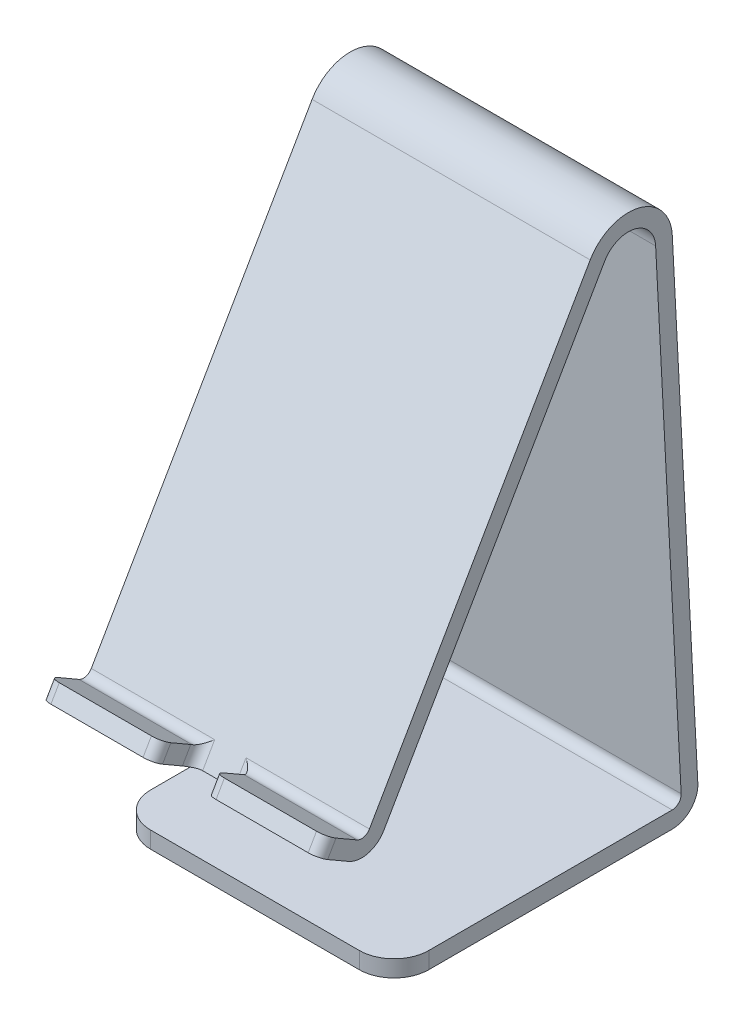
SolidWorks part; units mm, degrees
material "6061-T6 (SS)"
ref_plane "Front Plane" through (0, 0, 0) normal (0, 0, 1) x (1, 0, 0)
ref_plane "Top Plane" through (0, 0, 0) normal (0, 1, 0) x (1, 0, 0)
ref_plane "Right Plane" through (0, 0, 0) normal (1, 0, 0) x (0, 0, -1)
sketch "Sketch1" plane through (0, 0, 0) normal (1, 0, 0) x (0, 0, -1)
  line L0 (-45, 40) -> (18.5085, 150)
  line L1 (-40, 0) -> (40, 0)
  line L2 (-51.8301, 38.1699) -> (-47.5, 35.6699) construction
  line L3 (-47.5, 35.6699) -> (-45, 40) construction
  line L4 (44.9931, 5.2617) -> (37.6486, 145.4049)
  line L5 (44.9931, 5.2617) -> (44.9931, 137.2531) construction
  line L6 (-51.8301, 38.1699) -> (-60.4904, 43.1699)
  arc A0 (-45, 40) -> (-51.8301, 38.1699) centre (-49.3301, 42.5) cw
  arc A1 (18.5085, 150) -> (37.6486, 145.4049) centre (27.398, 144.8677) cw
  arc A2 (40, 0) -> (44.9931, 5.2617) centre (40, 5) ccw
  point P4 (0, 0)
  point P6 (0, 0)
  point P7 (0, 0)
  dimension "D2" = 40
  dimension "D7" = 150
  dimension "D6" = 5
  dimension "D1" = 80
  dimension "D3" = 5
  dimension "D4" = 60
  dimension "D5" = 5
  dimension "D8" = 3
  dimension "D9" = 10
surface "Surface-Extrude1" sketch "Sketch1" parameters "D1"=80
sketch "Sketch2" plane through (0, 0, 0) normal (0, 1, 0) x (1, 0, 0)
  line L0 (40, -40) -> (35.107, 40)
  line L2 (35.107, 40) -> (40, 40)
  line L3 (40, 40) -> (40, -40)
  line L4 (40, 40) -> (-40, 40) construction
  line L5 (0, 40) -> (0, -100) construction
  line L6 (-35.107, 40) -> (-40, 40)
  line L7 (-40, -40) -> (-35.107, 40)
  line L8 (-40, 40) -> (-40, -40)
  dimension "D1" = 3.5
surface "Surface-Trim1" [suppressed]
sketch3d "3DSketch1" [suppressed]
  line L0 (40, 5.2617, -44.9931) -> (-40, 5.2617, -44.9931) construction
  line L1 (40, 0, 40) -> (35.107, 0, -40) construction
  line L2 (-35.107, 0, -40) -> (-40, 0, -40)
  line L3 (-34.5773, 5.2617, -44.9931) -> (-40, 5.2617, -44.9931)
  line L4 (-35.107, 0, -40) -> (-40, 0, 40) construction
  line L7 (34.5773, 5.2617, -44.9931) -> (40, 5.2617, -44.9931)
  line L8 (35.107, 0, -40) -> (40, 0, -40)
  arc A1 (40, 0, -40) -> (40, 5.2617, -44.9931) centre (40, 5, -40) ccw construction
  arc A5 (40, 0, -40) -> (40, 5.2617, -44.9931) centre (40, 5, -40) ccw
  arc A6 (34.5773, 5.2617, -44.9931) -> (35.107, 0, -40) centre (34.8939, 5.0176, -39.987) cw
  arc A7 (-35.107, 0, -40) -> (-34.5773, 5.2617, -44.9931) centre (-34.8939, 5.0176, -39.987) ccw
  arc A8 (-40, 5.2617, -44.9931) -> (-40, 0, -40) centre (-40, 5, -40) cw
  point P1 (34.8189, 1.557, -43.6257)
  point P2 (45, 5, -40)
  point P10 (29.8857, 4.8041, -39.6807)
  point P17 (-29.8857, 4.8041, -39.6807)
  point P21 (45, 5, -40)
  point P23 (-45, 5, -40)
surface "Surface-Trim2" [suppressed]
sketch "Sketch5" plane through (0, 29.4856, 51.0705) normal (0, -0.5, -0.866) x (1, 0, 0)
  line L13 (-40, -12.141) -> (-40, -139.1581)
  line L14 (-40, -139.1581) -> (-35.5645, -139.1581)
  line L15 (40, -139.1581) -> (-40, -139.1581) construction
  line L16 (-35.5645, -139.1581) -> (-40, -12.141)
  line L17 (0, -60.0066) -> (0, 60.0066) construction
  line L18 (40, -139.1581) -> (35.5645, -139.1581)
  line L19 (40, -12.141) -> (40, -139.1581)
  line L20 (35.5645, -139.1581) -> (40, -12.141)
  dimension "D1" = 2
surface "Surface-Trim4" [suppressed]
sketch3d "3DSketch2" [suppressed]
  line L0 (40, 145.4049, -37.6486) -> (-40, 145.4049, -37.6486) construction
  line L2 (35.5645, 145.4049, -37.6486) -> (40, 145.4049, -37.6486)
  line L3 (35.5645, 150, -18.5085) -> (40, 150, -18.5085)
  line L4 (-35.5645, 150, -18.5085) -> (-40, 150, -18.5085)
  line L5 (-35.5645, 145.4049, -37.6486) -> (-40, 145.4049, -37.6486)
  arc A0 (35.5645, 150, -18.5085) -> (35.5645, 145.4049, -37.6486) centre (35.5645, 144.8677, -27.398) cw
  arc A1 (40, 145.4049, -37.6486) -> (40, 150, -18.5085) centre (40, 144.8677, -27.398) ccw construction
  arc A2 (40, 145.4049, -37.6486) -> (40, 150, -18.5085) centre (40, 144.8677, -27.398) ccw
  arc A3 (-40, 150, -18.5085) -> (-40, 145.4049, -37.6486) centre (-40, 144.8677, -27.398) cw
  arc A4 (-35.5645, 145.4049, -37.6486) -> (-35.5645, 150, -18.5085) centre (-35.5645, 144.8677, -27.398) ccw
  point P2 (25.2998, 144.8677, -27.398)
  point P8 (35.5645, 134.8866, -25.0017)
  point P15 (50.2646, 144.8677, -27.398)
  point P16 (50.2646, 144.8677, -27.398)
  point P19 (-50.2646, 144.8677, -27.398)
  point P23 (-25.2998, 144.8677, -27.398)
surface "Surface-Trim5" [suppressed]
sketch "Sketch4" [suppressed] plane through (0, 2.3659, -45.1449) normal (0, -0.0523, 0.9986) x (1, 0, 0)
  line L8 (40, 2.8997) -> (40, 143.2352) construction
  line L15 (40, 143.2352) -> (40, 2.8997)
  line L18 (34.5773, 2.8997) -> (40, 2.8997) construction
  line L19 (40, 2.8997) -> (34.5773, 2.8997)
  line L21 (35.5645, 143.2352) -> (34.5773, 2.8997)
  line L22 (35.5645, 143.2352) -> (40, 143.2352)
  line L28 (34.5773, 2.8997) -> (-34.5773, 2.8997) construction
  line L29 (0, -55) -> (0, 55) construction
  line L30 (-35.5645, 143.2352) -> (-40, 143.2352)
  line L31 (-35.5645, 143.2352) -> (-34.5773, 2.8997)
  line L32 (-40, 2.8997) -> (-34.5773, 2.8997)
  line L33 (-40, 143.2352) -> (-40, 2.8997)
surface "Surface-Trim6" [suppressed]
sketch3d "3DSketch3" [suppressed]
  line L0 (-45, 20, 65) -> (-20, 60, 130)
  line L1 (45, 20, 65) -> (-45, 20, 65) construction
  line L2 (-45, 20, 76.3137) -> (-20, 64.7814, 140.2537)
  line L3 (45, 20, 76.3137) -> (-45, 20, 76.3137) construction
  line L4 (-20, 60, 130) -> (-20, 64.7814, 140.2537) construction
  line L11 (20, 60, 130) -> (20, 64.7814, 140.2537) construction
  line L12 (45, 20, 76.3137) -> (20, 64.7814, 140.2537)
  line L13 (45, 20, 65) -> (20, 60, 130)
  line L14 (-20, 59.8831, 135.1269) -> (-20, 62.3907, 135.1269) construction
  arc A0 (-45, 20, 65) -> (-45, 20, 76.3137) centre (-45, 25.6569, 70.6569) cw
  arc A1 (20, 60, 130) -> (20, 64.7814, 140.2537) centre (20, 67.5175, 132.7362) ccw
  arc A2 (-45, 20, 65) -> (-45, 20, 76.3137) centre (-45, 25.6569, 70.6569) ccw construction
  arc A3 (-20, 64.7814, 140.2537) -> (-20, 60, 130) centre (-20, 67.5175, 132.7362) cw
  arc A4 (45, 20, 76.3137) -> (45, 20, 65) centre (45, 25.6569, 70.6569) ccw
  point P11 (-53, 25.6569, 70.6569)
  point P15 (-53, 25.6569, 70.6569)
  point P17 (-12, 67.5175, 132.7362)
  point P18 (-20, 60.2671, 136.1171)
  point P30 (12, 67.5175, 132.7362)
  point P34 (53, 25.6569, 70.6569)
  dimension "D1" = 40
thicken "Thicken1" surfaces to thicken 101 thickness 2.4 thickness side both sides parameters "D1"=2.4
sketch "Sketch7" plane through (0, 30.6856, 53.149) normal (0, 0.5, 0.866) x (1, 0, 0)
  line L0 (-30.736, 134.1581) -> (0, 1014.3226) construction
  line L1 (30.736, 134.1581) -> (0, 1014.3226) construction
  line L2 (-13.7263, 133.5739) -> (-7.783, 120.5739)
  line L3 (-23.2255, 120.6692) -> (-15.4953, 133.6692)
  line L5 (-8.6925, 119.1581) -> (-22.366, 119.1581)
  line L6 (-6.8527, 132.7423) -> (-0.9095, 119.7423)
  line L7 (0.9095, 119.7423) -> (6.8527, 132.7423)
  line L8 (5.9433, 134.1581) -> (-5.9433, 134.1581)
  line L11 (31.2237, 120.193) -> (30.7697, 133.193)
  line L12 (29.3648, 119.647) -> (21.6346, 132.647)
  line L13 (-30.7697, 133.193) -> (-31.2237, 120.193)
  line L14 (-29.3648, 119.647) -> (-21.6346, 132.647)
  line L15 (-22.4941, 134.1581) -> (-29.7703, 134.1581)
  line L17 (-34.8223, 17.141) -> (34.8223, 17.141)
  line L18 (34.8223, 17.141) -> (30.736, 134.1581)
  line L19 (30.736, 134.1581) -> (-30.736, 134.1581)
  line L20 (-30.736, 134.1581) -> (-34.8223, 17.141)
  line L21 (-34.8223, 17.141) -> (34.8223, 17.141) construction
  line L22 (34.8223, 17.141) -> (30.736, 134.1581) construction
  line L23 (30.736, 134.1581) -> (-30.736, 134.1581) construction
  line L24 (-30.736, 134.1581) -> (-34.8223, 17.141) construction
  line L27 (22.4941, 134.1581) -> (29.7703, 134.1581)
  line L28 (13.7263, 133.5739) -> (7.783, 120.5739)
  line L29 (8.6925, 119.1581) -> (22.366, 119.1581)
  line L30 (23.2255, 120.6692) -> (15.4953, 133.6692)
  line L31 (0, 17.141) -> (0, 1014.3226) construction
  line L32 (-31.2598, 119.1581) -> (-24.1241, 119.1581)
  line L33 (-7.1358, 119.1581) -> (0, 119.1581)
  line L34 (7.1358, 119.1581) -> (0, 119.1581)
  line L35 (24.1241, 119.1581) -> (31.2598, 119.1581)
  line L36 (-31.3646, 116.1581) -> (31.3646, 116.1581) construction
  line L43 (0.9023, 112.5892) -> (7.1135, 99.5892)
  line L44 (-7.1135, 99.5892) -> (-0.9023, 112.5892)
  line L45 (6.2112, 98.1581) -> (-6.2112, 98.1581)
  line L46 (-22.7888, 111.6746) -> (-15.6085, 98.6746)
  line L47 (-8.522, 113.1581) -> (-21.9134, 113.1581)
  line L48 (-13.8309, 98.727) -> (-7.6197, 111.727)
  line L49 (-29.6283, 112.6416) -> (-22.4481, 99.6416)
  line L50 (-31.957, 99.193) -> (-31.5031, 112.193)
  line L51 (-23.3234, 98.1581) -> (-30.9576, 98.1581)
  line L52 (-31.9932, 98.1581) -> (31.9932, 98.1581) construction
  line L53 (-31.4694, 113.1581) -> (31.4694, 113.1581) construction
  line L54 (0, 1014.3226) -> (-24.3237, 17.141) construction
  line L55 (0, 1014.3226) -> (-7.8575, 17.141) construction
  line L56 (-29.9136, 113.1581) -> (-23.6081, 113.1581)
  line L57 (-6.9359, 113.1581) -> (-0.6305, 113.1581)
  line L58 (8.522, 113.1581) -> (21.9134, 113.1581)
  line L59 (13.8309, 98.727) -> (7.6197, 111.727)
  line L60 (22.7888, 111.6746) -> (15.6085, 98.6746)
  line L61 (31.957, 99.193) -> (31.5031, 112.193)
  line L62 (23.3234, 98.1581) -> (30.9576, 98.1581)
  line L63 (29.6283, 112.6416) -> (22.4481, 99.6416)
  line L64 (-32.0979, 95.1581) -> (32.0979, 95.1581) construction
  line L65 (-7.1748, 90.7234) -> (-0.9006, 77.7234)
  line L66 (6.2742, 92.1581) -> (-6.2742, 92.1581)
  line L67 (0.9006, 77.7234) -> (7.1748, 90.7234)
  line L68 (-8.5514, 77.1581) -> (-22.998, 77.1581)
  line L69 (-13.925, 91.5927) -> (-7.6508, 78.5927)
  line L70 (-23.8446, 78.6903) -> (-15.6722, 91.6903)
  line L71 (-32.2364, 91.193) -> (-32.6904, 78.193)
  line L72 (-23.5186, 92.1581) -> (-31.237, 92.1581)
  line L73 (-30.8444, 77.6259) -> (-22.672, 90.6259)
  line L74 (-32.2027, 92.1581) -> (32.2027, 92.1581) construction
  line L75 (-32.7265, 77.1581) -> (32.7265, 77.1581) construction
  line L76 (-21.7087, 92.1581) -> (-15.3781, 92.1581)
  line L77 (-14.1978, 92.1581) -> (-7.8672, 92.1581)
  line L78 (32.2364, 91.193) -> (32.6904, 78.193)
  line L79 (23.5186, 92.1581) -> (31.237, 92.1581)
  line L80 (30.8444, 77.6259) -> (22.672, 90.6259)
  line L81 (23.8446, 78.6903) -> (15.6722, 91.6903)
  line L82 (13.925, 91.5927) -> (7.6508, 78.5927)
  line L83 (8.5514, 77.1581) -> (22.998, 77.1581)
  line L84 (-32.8313, 74.1581) -> (32.8313, 74.1581) construction
  line L85 (-7.4354, 57.6076) -> (-0.8933, 70.6076)
  line L86 (6.5421, 56.1581) -> (-6.5421, 56.1581)
  line L87 (0.8933, 70.6076) -> (7.4354, 57.6076)
  line L88 (-23.8904, 69.6523) -> (-16.2679, 56.6523)
  line L89 (-14.512, 56.7085) -> (-7.9699, 69.7085)
  line L90 (-8.8632, 71.1581) -> (-23.0277, 71.1581)
  line L91 (-33.4237, 57.193) -> (-32.9697, 70.193)
  line L92 (-24.3479, 56.1581) -> (-32.4243, 56.1581)
  line L93 (-31.1077, 70.6639) -> (-23.4853, 57.6639)
  line L94 (-32.936, 71.1581) -> (32.936, 71.1581) construction
  line L95 (-33.4598, 56.1581) -> (33.4598, 56.1581) construction
  line L96 (-31.3975, 71.1581) -> (-24.7733, 71.1581)
  line L97 (-7.2404, 71.1581) -> (-0.6162, 71.1581)
  line L98 (24.3479, 56.1581) -> (32.4243, 56.1581)
  line L99 (31.1077, 70.6639) -> (23.4853, 57.6639)
  line L100 (33.4237, 57.193) -> (32.9697, 70.193)
  line L101 (8.8632, 71.1581) -> (23.0277, 71.1581)
  line L102 (14.512, 56.7085) -> (7.9699, 69.7085)
  line L103 (23.8904, 69.6523) -> (16.2679, 56.6523)
  line L104 (-33.5646, 53.1581) -> (33.5646, 53.1581) construction
  line L105 (6.6053, 50.1581) -> (-6.6053, 50.1581)
  line L106 (0.8914, 35.705) -> (7.4967, 48.7053)
  line L107 (-7.4967, 48.7053) -> (-0.8914, 35.705)
  line L108 (-8.8909, 35.1581) -> (-24.111, 35.1581)
  line L109 (-14.6047, 49.6111) -> (-7.9995, 36.6109)
  line L110 (-24.9445, 36.7103) -> (-16.3296, 49.7105)
  line L111 (-24.5429, 50.1581) -> (-32.7038, 50.1581)
  line L112 (-32.3243, 35.6056) -> (-23.7095, 48.6059)
  line L113 (-33.7031, 49.1931) -> (-34.157, 36.1929)
  line L114 (-33.6694, 50.1581) -> (33.6694, 50.1581) construction
  line L115 (-34.1932, 35.1581) -> (34.1932, 35.1581) construction
  line L116 (-22.6809, 50.1581) -> (-16.0331, 50.1581)
  line L117 (-14.8826, 50.1581) -> (-8.2349, 50.1581)
  line L118 (24.9445, 36.7103) -> (16.3296, 49.7105)
  line L119 (14.6047, 49.6111) -> (7.9995, 36.6109)
  line L120 (8.8909, 35.1581) -> (24.111, 35.1581)
  line L121 (33.7031, 49.1931) -> (34.157, 36.1929)
  line L122 (32.3243, 35.6056) -> (23.7095, 48.6059)
  line L123 (24.5429, 50.1581) -> (32.7038, 50.1581)
  line L124 (-34.2979, 32.1581) -> (34.2979, 32.1581) construction
  line L128 (-24.9916, 27.6311) -> (-16.9268, 14.6309)
  line L129 (-15.1932, 14.6906) -> (-8.32, 27.6909)
  line L130 (-9.2039, 29.1581) -> (-24.142, 29.1581)
  line L131 (-34.8904, 15.1929) -> (-34.4364, 28.1931)
  line L132 (-32.5875, 28.6853) -> (-24.5226, 15.6851)
  line L133 (-25.3723, 14.1581) -> (-33.8911, 14.1581)
  line L134 (-34.4027, 29.1581) -> (34.4027, 29.1581) construction
  line L135 (-34.9265, 14.1581) -> (34.9265, 14.1581) construction
  line L136 (-7.7571, 15.6253) -> (-0.8839, 28.6255)
  line L137 (0.8839, 28.6255) -> (7.7571, 15.6253)
  line L138 (6.8732, 14.1581) -> (-6.8732, 14.1581)
  line L139 (-32.8808, 29.1581) -> (-25.9389, 29.1581)
  line L140 (-7.5443, 29.1581) -> (-0.6024, 29.1581)
  line L141 (25.3723, 14.1581) -> (33.8911, 14.1581)
  line L142 (32.5875, 28.6853) -> (24.5226, 15.6851)
  line L143 (34.8904, 15.1929) -> (34.4364, 28.1931)
  line L144 (9.2039, 29.1581) -> (24.142, 29.1581)
  line L145 (15.1932, 14.6906) -> (8.32, 27.6909)
  line L146 (24.9916, 27.6311) -> (16.9268, 14.6309)
  arc A0 (-31.2237, 120.193) -> (-29.3648, 119.647) centre (-30.2243, 120.1581) ccw
  arc A1 (-7.783, 120.5739) -> (-8.6925, 119.1581) centre (-8.6925, 120.1581) cw
  arc A2 (-23.2255, 120.6692) -> (-22.366, 119.1581) centre (-22.366, 120.1581) ccw
  arc A3 (29.7703, 134.1581) -> (30.7697, 133.193) centre (29.7703, 133.1581) cw
  arc A4 (21.6346, 132.647) -> (22.4941, 134.1581) centre (22.4941, 133.1581) cw
  arc A5 (29.3648, 119.647) -> (31.2237, 120.193) centre (30.2243, 120.1581) ccw
  arc A6 (22.366, 119.1581) -> (23.2255, 120.6692) centre (22.366, 120.1581) ccw
  arc A7 (13.7263, 133.5739) -> (15.4953, 133.6692) centre (14.6358, 133.1581) cw
  arc A8 (7.783, 120.5739) -> (8.6925, 119.1581) centre (8.6925, 120.1581) ccw
  arc A9 (6.8527, 132.7423) -> (5.9433, 134.1581) centre (5.9433, 133.1581) ccw
  arc A10 (-0.9095, 119.7423) -> (0.9095, 119.7423) centre (0, 120.1581) ccw
  arc A11 (-6.8527, 132.7423) -> (-5.9433, 134.1581) centre (-5.9433, 133.1581) cw
  arc A12 (-15.4953, 133.6692) -> (-13.7263, 133.5739) centre (-14.6358, 133.1581) cw
  arc A13 (-21.6346, 132.647) -> (-22.4941, 134.1581) centre (-22.4941, 133.1581) ccw
  arc A14 (-30.7697, 133.193) -> (-29.7703, 134.1581) centre (-29.7703, 133.1581) cw
  arc A21 (-0.9023, 112.5892) -> (0.9023, 112.5892) centre (0, 112.1581) cw
  arc A22 (7.1135, 99.5892) -> (6.2112, 98.1581) centre (6.2112, 99.1581) cw
  arc A23 (-7.1135, 99.5892) -> (-6.2112, 98.1581) centre (-6.2112, 99.1581) ccw
  arc A24 (-22.7888, 111.6746) -> (-21.9134, 113.1581) centre (-21.9134, 112.1581) cw
  arc A25 (-7.6197, 111.727) -> (-8.522, 113.1581) centre (-8.522, 112.1581) ccw
  arc A26 (-15.6085, 98.6746) -> (-13.8309, 98.727) centre (-14.7332, 99.1581) ccw
  arc A27 (-31.5031, 112.193) -> (-29.6283, 112.6416) centre (-30.5037, 112.1581) cw
  arc A28 (-22.4481, 99.6416) -> (-23.3234, 98.1581) centre (-23.3234, 99.1581) cw
  arc A29 (-31.957, 99.193) -> (-30.9576, 98.1581) centre (-30.9576, 99.1581) ccw
  arc A30 (22.7888, 111.6746) -> (21.9134, 113.1581) centre (21.9134, 112.1581) ccw
  arc A31 (7.6197, 111.727) -> (8.522, 113.1581) centre (8.522, 112.1581) cw
  arc A32 (15.6085, 98.6746) -> (13.8309, 98.727) centre (14.7332, 99.1581) cw
  arc A33 (31.5031, 112.193) -> (29.6283, 112.6416) centre (30.5037, 112.1581) ccw
  arc A34 (31.957, 99.193) -> (30.9576, 98.1581) centre (30.9576, 99.1581) cw
  arc A35 (22.4481, 99.6416) -> (23.3234, 98.1581) centre (23.3234, 99.1581) ccw
  arc A36 (-0.9006, 77.7234) -> (0.9006, 77.7234) centre (0, 78.1581) ccw
  arc A37 (-7.1748, 90.7234) -> (-6.2742, 92.1581) centre (-6.2742, 91.1581) cw
  arc A38 (7.1748, 90.7234) -> (6.2742, 92.1581) centre (6.2742, 91.1581) ccw
  arc A39 (-23.8446, 78.6903) -> (-22.998, 77.1581) centre (-22.998, 78.1581) ccw
  arc A40 (-7.6508, 78.5927) -> (-8.5514, 77.1581) centre (-8.5514, 78.1581) cw
  arc A41 (-15.6722, 91.6903) -> (-13.925, 91.5927) centre (-14.8256, 91.1581) cw
  arc A42 (-32.6904, 78.193) -> (-30.8444, 77.6259) centre (-31.691, 78.1581) ccw
  arc A43 (-32.2364, 91.193) -> (-31.237, 92.1581) centre (-31.237, 91.1581) cw
  arc A44 (-22.672, 90.6259) -> (-23.5186, 92.1581) centre (-23.5186, 91.1581) ccw
  arc A45 (32.2364, 91.193) -> (31.237, 92.1581) centre (31.237, 91.1581) ccw
  arc A46 (22.672, 90.6259) -> (23.5186, 92.1581) centre (23.5186, 91.1581) cw
  arc A47 (32.6904, 78.193) -> (30.8444, 77.6259) centre (31.691, 78.1581) cw
  arc A48 (15.6722, 91.6903) -> (13.925, 91.5927) centre (14.8256, 91.1581) ccw
  arc A49 (7.6508, 78.5927) -> (8.5514, 77.1581) centre (8.5514, 78.1581) ccw
  arc A50 (23.8446, 78.6903) -> (22.998, 77.1581) centre (22.998, 78.1581) cw
  arc A51 (-7.4354, 57.6076) -> (-6.5421, 56.1581) centre (-6.5421, 57.1581) ccw
  arc A52 (7.4354, 57.6076) -> (6.5421, 56.1581) centre (6.5421, 57.1581) cw
  arc A53 (-0.8933, 70.6076) -> (0.8933, 70.6076) centre (0, 70.1581) cw
  arc A54 (-16.2679, 56.6523) -> (-14.512, 56.7085) centre (-15.4053, 57.1581) ccw
  arc A55 (-7.9699, 69.7085) -> (-8.8632, 71.1581) centre (-8.8632, 70.1581) ccw
  arc A56 (-23.8904, 69.6523) -> (-23.0277, 71.1581) centre (-23.0277, 70.1581) cw
  arc A57 (-33.4237, 57.193) -> (-32.4243, 56.1581) centre (-32.4243, 57.1581) ccw
  arc A58 (-23.4853, 57.6639) -> (-24.3479, 56.1581) centre (-24.3479, 57.1581) cw
  arc A59 (-32.9697, 70.193) -> (-31.1077, 70.6639) centre (-31.9703, 70.1581) cw
  arc A60 (33.4237, 57.193) -> (32.4243, 56.1581) centre (32.4243, 57.1581) cw
  arc A61 (23.4853, 57.6639) -> (24.3479, 56.1581) centre (24.3479, 57.1581) ccw
  arc A62 (32.9697, 70.193) -> (31.1077, 70.6639) centre (31.9703, 70.1581) ccw
  arc A63 (23.8904, 69.6523) -> (23.0277, 71.1581) centre (23.0277, 70.1581) ccw
  arc A64 (7.9699, 69.7085) -> (8.8632, 71.1581) centre (8.8632, 70.1581) cw
  arc A65 (16.2679, 56.6523) -> (14.512, 56.7085) centre (15.4053, 57.1581) cw
  arc A66 (-7.4967, 48.7053) -> (-6.6053, 50.1581) centre (-6.6053, 49.1582) cw
  arc A67 (7.4967, 48.7053) -> (6.6053, 50.1581) centre (6.6053, 49.1582) ccw
  arc A68 (-0.8914, 35.705) -> (0.8914, 35.705) centre (0, 36.158) ccw
  arc A69 (-24.9445, 36.7103) -> (-24.111, 35.1581) centre (-24.111, 36.158) ccw
  arc A70 (-7.9995, 36.6109) -> (-8.8909, 35.1581) centre (-8.8909, 36.158) cw
  arc A71 (-16.3296, 49.7105) -> (-14.6047, 49.6111) centre (-15.4962, 49.1582) cw
  arc A72 (-33.7031, 49.1931) -> (-32.7038, 50.1581) centre (-32.7038, 49.1582) cw
  arc A73 (-23.7095, 48.6059) -> (-24.5429, 50.1581) centre (-24.5429, 49.1582) ccw
  arc A74 (-34.157, 36.1929) -> (-32.3243, 35.6056) centre (-33.1578, 36.158) ccw
  arc A75 (16.3296, 49.7105) -> (14.6047, 49.6111) centre (15.4962, 49.1582) ccw
  arc A76 (7.9995, 36.6109) -> (8.8909, 35.1581) centre (8.8909, 36.158) ccw
  arc A77 (24.9445, 36.7103) -> (24.111, 35.1581) centre (24.111, 36.158) cw
  arc A78 (34.157, 36.1929) -> (32.3243, 35.6056) centre (33.1578, 36.158) cw
  arc A79 (23.7095, 48.6059) -> (24.5429, 50.1581) centre (24.5429, 49.1582) cw
  arc A80 (33.7031, 49.1931) -> (32.7038, 50.1581) centre (32.7038, 49.1582) ccw
  arc A84 (-16.9268, 14.6309) -> (-15.1932, 14.6906) centre (-16.0771, 15.158) ccw
  arc A85 (-8.32, 27.6909) -> (-9.2039, 29.1581) centre (-9.2039, 28.1582) ccw
  arc A86 (-24.9916, 27.6311) -> (-24.142, 29.1581) centre (-24.142, 28.1582) cw
  arc A87 (-34.4364, 28.1931) -> (-32.5875, 28.6853) centre (-33.4371, 28.1582) cw
  arc A88 (-24.5226, 15.6851) -> (-25.3723, 14.1581) centre (-25.3723, 15.158) cw
  arc A89 (-34.8904, 15.1929) -> (-33.8911, 14.1581) centre (-33.8911, 15.158) ccw
  arc A90 (-0.8839, 28.6255) -> (0.8839, 28.6255) centre (0, 28.1582) cw
  arc A91 (7.7571, 15.6253) -> (6.8732, 14.1581) centre (6.8732, 15.158) cw
  arc A92 (-7.7571, 15.6253) -> (-6.8732, 14.1581) centre (-6.8732, 15.158) ccw
  arc A93 (34.8904, 15.1929) -> (33.8911, 14.1581) centre (33.8911, 15.158) cw
  arc A94 (24.5226, 15.6851) -> (25.3723, 14.1581) centre (25.3723, 15.158) ccw
  arc A95 (34.4364, 28.1931) -> (32.5875, 28.6853) centre (33.4371, 28.1582) ccw
  arc A96 (24.9916, 27.6311) -> (24.142, 29.1581) centre (24.142, 28.1582) ccw
  arc A97 (8.32, 27.6909) -> (9.2039, 29.1581) centre (9.2039, 28.1582) cw
  arc A98 (16.9268, 14.6309) -> (15.1932, 14.6906) centre (16.0771, 15.158) cw
  point P22 (0, 134.1581)
  point P36 (20.736, 134.1581)
  point P51 (7.5, 134.1581)
  point P57 (-7.5, 134.1581)
  point P63 (-20.736, 134.1581)
  dimension "D6" = 1
  dimension "D9" = 1
  dimension "D13" = 1
  dimension "D18" = 1
  dimension "D22" = 0.9999
  dimension "D26" = 0.9999
  dimension "D3" = 10
  dimension "D4" = 15
  dimension "D5" = 10
  dimension "D7" = 3
  dimension "D10" = 3
  dimension "D11" = 3
  dimension "D12" = 3
  dimension "D15" = 3
  dimension "D16" = 3
  dimension "D19" = 3
  dimension "D20" = 3
  dimension "D23" = 3
  dimension "D24" = 3
  dimension "D8" = 15
  dimension "D14" = 15
  dimension "D17" = 15
  dimension "D21" = 15
  dimension "D25" = 15
  dimension "D27" = 15
  dimension "D1" = 5
extrude "Cut-Extrude1" [suppressed] cut sketch "Sketch7" against normal up to surface (4.8 mm away) contours L14 L15 L13 | L5 L2 L3 | L7 L8 L6 | L29 L30 L28 | L27 L12 L11 | L50 A29 L51 A28 L49 A27 | L46 A26 L48 A25 L47 A24 | L44 A23 L45 A22 L43 A21 | A32 L60 A30 L58 A31 L59 | L63 A35 L62 A34 L61 A33 | L73 A44 L72 A43 L71 A42 | A41 L70 A39 L68 A40 L69 | L67 A38 L66 A37 L65 A36 | A50 L81 A48 L82 A49 L83 | A47 L78 A45 L79 A46 L80 | L100 A62 L99 A61 L98 A60 | A65 L103 A63 L101 A64 L102 | A53 L85 A51 L86 A52 L87 | A56 L88 A54 L89 A55 L90 | A59 L91 A57 L92 A58 L93 | L113 A74 L112 A73 L111 A72 | A71 L110 A69 L108 A70 L109 | L107 A68 L106 A67 L105 A66 | A77 L118 A75 L119 A76 L120 | L121 A80 L123 A79 L122 A78 | L143 A95 L142 A94 L141 A93 | A98 L146 A96 L144 A97 L145 | L136 A92 L138 A91 L137 A90 | A86 L128 A84 L129 A85 L130 | L131 A89 L133 A88 L132 A87
sketch "Sketch8" plane through (0, 2.4916, -47.5416) normal (0, 0.0523, -0.9986) x (-1, 0, 0)
  line L3 (-27.4587, 128.2282) -> (-27.5572, 142.2282)
  line L4 (-26.5572, 143.2352) -> (-20.5571, 143.2352)
  line L5 (-19.6356, 141.8468) -> (-25.5373, 127.8468)
  line L8 (0, 143.2352) -> (0, 4.8997) construction
  line L9 (-27.4517, 127.2352) -> (27.4517, 127.2352) construction
  line L12 (-40, 143.2352) -> (40, 143.2352) construction
  line L13 (34.5773, 2.8997) -> (35.5645, 143.2352) construction
  line L14 (-35.5645, 143.2352) -> (-34.5773, 2.8997) construction
  line L15 (-40, 2.8997) -> (40, 2.8997) construction
  line L16 (26.5912, 4.8997) -> (27.5643, 143.2352) construction
  line L17 (27.5643, 143.2352) -> (-27.5643, 143.2352) construction
  line L18 (-27.5643, 143.2352) -> (-26.5912, 4.8997) construction
  line L19 (-26.5912, 4.8997) -> (26.5912, 4.8997) construction
  line L22 (-14.1508, 142.6237) -> (-20.0525, 128.6237)
  line L23 (-19.131, 127.2352) -> (-7.3277, 127.2352)
  line L24 (-6.4062, 128.6237) -> (-12.3079, 142.6237)
  line L25 (-13.2294, 127.2352) -> (-13.2294, 142.2352)
  line L26 (-19.0503, 143.2352) -> (-13.893, 143.2352)
  line L27 (-6.8231, 141.8468) -> (-0.9215, 127.8468)
  line L28 (0.9215, 127.8468) -> (6.8231, 141.8468)
  line L29 (5.9017, 143.2352) -> (-5.9017, 143.2352)
  line L30 (-12.5657, 143.2352) -> (-7.4084, 143.2352)
  line L31 (-0.9215, 127.8468) -> (-6.8231, 141.8468)
  line L32 (6.8231, 141.8468) -> (0.9215, 127.8468)
  line L33 (19.131, 127.2352) -> (7.3277, 127.2352)
  line L34 (14.1508, 142.6237) -> (20.0525, 128.6237)
  line L35 (6.4062, 128.6237) -> (12.3079, 142.6237)
  line L36 (26.5572, 143.2352) -> (20.5571, 143.2352)
  line L37 (27.4587, 128.2282) -> (27.5572, 142.2282)
  line L38 (19.6356, 141.8468) -> (25.5373, 127.8468)
  line L39 (-27.4306, 124.2352) -> (27.4306, 124.2352) construction
  line L40 (-26.5572, 105.2352) -> (-20.5571, 105.2352)
  line L41 (-27.4587, 120.2423) -> (-27.5572, 106.2423)
  line L42 (-19.6356, 106.6237) -> (-25.5373, 120.6237)
  line L43 (-19.131, 121.2352) -> (-7.3277, 121.2352)
  line L44 (-14.1508, 105.8468) -> (-20.0525, 119.8468)
  line L45 (-6.4062, 119.8468) -> (-12.3079, 105.8468)
  line L46 (0.9215, 120.6237) -> (6.8231, 106.6237)
  line L47 (-6.8231, 106.6237) -> (-0.9215, 120.6237)
  line L48 (5.9017, 105.2352) -> (-5.9017, 105.2352)
  line L49 (14.1508, 105.8468) -> (20.0525, 119.8468)
  line L50 (6.4062, 119.8468) -> (12.3079, 105.8468)
  line L51 (19.131, 121.2352) -> (7.3277, 121.2352)
  line L52 (27.4587, 120.2423) -> (27.5572, 106.2423)
  line L53 (19.6356, 106.6237) -> (25.5373, 120.6237)
  line L54 (26.5572, 105.2352) -> (20.5571, 105.2352)
  line L55 (-27.2759, 102.2352) -> (27.2759, 102.2352) construction
  line L56 (-26.5572, 61.2352) -> (-20.5571, 61.2352)
  line L57 (-27.4587, 76.2423) -> (-27.5572, 62.2423)
  line L58 (-19.6356, 62.6237) -> (-25.5373, 76.6237)
  line L59 (-19.131, 77.2352) -> (-7.3277, 77.2352)
  line L60 (-14.1508, 61.8468) -> (-20.0525, 75.8468)
  line L61 (-6.4062, 75.8468) -> (-12.3079, 61.8468)
  line L62 (0.9215, 76.6237) -> (6.8231, 62.6237)
  line L63 (-6.8231, 62.6237) -> (-0.9215, 76.6237)
  line L64 (5.9017, 61.2352) -> (-5.9017, 61.2352)
  line L65 (14.1508, 61.8468) -> (20.0525, 75.8468)
  line L66 (6.4062, 75.8468) -> (12.3079, 61.8468)
  line L67 (19.131, 77.2352) -> (7.3277, 77.2352)
  line L68 (27.4587, 76.2423) -> (27.5572, 62.2423)
  line L69 (19.6356, 62.6237) -> (25.5373, 76.6237)
  line L70 (26.5572, 61.2352) -> (20.5571, 61.2352)
  line L71 (-27.4587, 84.2282) -> (-27.5572, 98.2282)
  line L72 (-19.6356, 97.8468) -> (-25.5373, 83.8468)
  line L73 (-26.5572, 99.2352) -> (-20.5571, 99.2352)
  line L74 (-14.1508, 98.6237) -> (-20.0525, 84.6237)
  line L75 (-6.4062, 84.6237) -> (-12.3079, 98.6237)
  line L76 (-19.131, 83.2352) -> (-7.3277, 83.2352)
  line L77 (-6.8231, 97.8468) -> (-0.9215, 83.8468)
  line L78 (5.9017, 99.2352) -> (-5.9017, 99.2352)
  line L79 (0.9215, 83.8468) -> (6.8231, 97.8468)
  line L80 (14.1508, 98.6237) -> (20.0525, 84.6237)
  line L81 (6.4062, 84.6237) -> (12.3079, 98.6237)
  line L82 (19.131, 83.2352) -> (7.3277, 83.2352)
  line L83 (27.4587, 84.2282) -> (27.5572, 98.2282)
  line L84 (19.6356, 97.8468) -> (25.5373, 83.8468)
  line L85 (26.5572, 99.2352) -> (20.5571, 99.2352)
  line L86 (-26.9664, 58.2352) -> (26.9664, 58.2352) construction
  line L87 (-19.6356, 9.8468) -> (-25.5373, -4.1532)
  line L88 (-27.4587, 40.2282) -> (-27.5572, 54.2282)
  line L89 (-19.6356, 53.8468) -> (-25.5373, 39.8468)
  line L90 (-26.5572, 55.2352) -> (-20.5571, 55.2352)
  line L91 (-14.1508, 54.6237) -> (-20.0525, 40.6237)
  line L92 (-6.4062, 40.6237) -> (-12.3079, 54.6237)
  line L93 (-19.131, 39.2352) -> (-7.3277, 39.2352)
  line L94 (-6.8231, 53.8468) -> (-0.9215, 39.8468)
  line L95 (5.9017, 55.2352) -> (-5.9017, 55.2352)
  line L96 (0.9215, 39.8468) -> (6.8231, 53.8468)
  line L97 (14.1508, 54.6237) -> (20.0525, 40.6237)
  line L98 (6.4062, 40.6237) -> (12.3079, 54.6237)
  line L99 (19.131, 39.2352) -> (7.3277, 39.2352)
  line L100 (27.4587, 40.2282) -> (27.5572, 54.2282)
  line L101 (19.6356, 53.8468) -> (25.5373, 39.8468)
  line L102 (26.5572, 55.2352) -> (20.5571, 55.2352)
  line L103 (19.6356, 18.6237) -> (25.5373, 32.6237)
  line L104 (26.5572, 17.2352) -> (20.5571, 17.2352)
  line L105 (27.4587, 32.2423) -> (27.5572, 18.2423)
  line L106 (6.4062, 31.8468) -> (12.3079, 17.8468)
  line L107 (19.131, 33.2352) -> (7.3277, 33.2352)
  line L108 (14.1508, 17.8468) -> (20.0525, 31.8468)
  line L109 (-6.8231, 18.6237) -> (-0.9215, 32.6237)
  line L110 (5.9017, 17.2352) -> (-5.9017, 17.2352)
  line L111 (0.9215, 32.6237) -> (6.8231, 18.6237)
  line L112 (-14.1508, 17.8468) -> (-20.0525, 31.8468)
  line L113 (-6.4062, 31.8468) -> (-12.3079, 17.8468)
  line L114 (-19.131, 33.2352) -> (-7.3277, 33.2352)
  line L115 (-27.4587, 32.2423) -> (-27.5572, 18.2423)
  line L116 (-19.6356, 18.6237) -> (-25.5373, 32.6237)
  line L117 (-26.5572, 17.2352) -> (-20.5571, 17.2352)
  line L118 (-26.6569, 14.2352) -> (26.6569, 14.2352) construction
  line L119 (-26.5572, 11.2352) -> (-20.5571, 11.2352)
  line L120 (-27.4587, -3.7718) -> (-27.5572, 10.2282)
  line L121 (-6.4062, -3.3763) -> (-12.3079, 10.6237)
  line L122 (-19.131, -4.7648) -> (-7.3277, -4.7648)
  line L123 (-14.1508, 10.6237) -> (-20.0525, -3.3763)
  line L124 (5.9017, 11.2352) -> (-5.9017, 11.2352)
  line L125 (0.9215, -4.1532) -> (6.8231, 9.8468)
  line L126 (-6.8231, 9.8468) -> (-0.9215, -4.1532)
  line L127 (14.1508, 10.6237) -> (20.0525, -3.3763)
  line L128 (19.131, -4.7648) -> (7.3277, -4.7648)
  line L129 (6.4062, -3.3763) -> (12.3079, 10.6237)
  line L130 (27.4587, -3.7718) -> (27.5572, 10.2282)
  line L131 (26.5572, 11.2352) -> (20.5571, 11.2352)
  line L132 (19.6356, 9.8468) -> (25.5373, -4.1532)
  arc A3 (-27.5572, 142.2282) -> (-26.5572, 143.2352) centre (-26.5572, 142.2352) cw
  arc A4 (-20.5571, 143.2352) -> (-19.6356, 141.8468) centre (-20.5571, 142.2352) cw
  arc A5 (-27.4587, 128.2282) -> (-25.5373, 127.8468) centre (-26.4587, 128.2352) ccw
  arc A12 (-7.3277, 127.2352) -> (-6.4062, 128.6237) centre (-7.3277, 128.2352) ccw
  arc A13 (-14.1508, 142.6237) -> (-12.3079, 142.6237) centre (-13.2294, 142.2352) cw
  arc A14 (-20.0525, 128.6237) -> (-19.131, 127.2352) centre (-19.131, 128.2352) ccw
  arc A15 (-0.9215, 127.8468) -> (0.9215, 127.8468) centre (0, 128.2352) ccw
  arc A16 (6.8231, 141.8468) -> (5.9017, 143.2352) centre (5.9017, 142.2352) ccw
  arc A17 (-6.8231, 141.8468) -> (-5.9017, 143.2352) centre (-5.9017, 142.2352) cw
  arc A18 (-6.8231, 141.8468) -> (-5.9017, 143.2352) centre (-5.9017, 142.2352) cw
  arc A19 (6.8231, 141.8468) -> (5.9017, 143.2352) centre (5.9017, 142.2352) ccw
  arc A20 (20.0525, 128.6237) -> (19.131, 127.2352) centre (19.131, 128.2352) cw
  arc A21 (7.3277, 127.2352) -> (6.4062, 128.6237) centre (7.3277, 128.2352) cw
  arc A22 (14.1508, 142.6237) -> (12.3079, 142.6237) centre (13.2294, 142.2352) ccw
  arc A23 (27.5572, 142.2282) -> (26.5572, 143.2352) centre (26.5572, 142.2352) ccw
  arc A24 (20.5571, 143.2352) -> (19.6356, 141.8468) centre (20.5571, 142.2352) ccw
  arc A25 (27.4587, 128.2282) -> (25.5373, 127.8468) centre (26.4587, 128.2352) cw
  arc A26 (-27.5572, 106.2423) -> (-26.5572, 105.2352) centre (-26.5572, 106.2352) ccw
  arc A27 (-20.5571, 105.2352) -> (-19.6356, 106.6237) centre (-20.5571, 106.2352) ccw
  arc A28 (-27.4587, 120.2423) -> (-25.5373, 120.6237) centre (-26.4587, 120.2352) cw
  arc A29 (-20.0525, 119.8468) -> (-19.131, 121.2352) centre (-19.131, 120.2352) cw
  arc A30 (-7.3277, 121.2352) -> (-6.4062, 119.8468) centre (-7.3277, 120.2352) cw
  arc A31 (-14.1508, 105.8468) -> (-12.3079, 105.8468) centre (-13.2294, 106.2352) ccw
  arc A32 (-0.9215, 120.6237) -> (0.9215, 120.6237) centre (0, 120.2352) cw
  arc A33 (6.8231, 106.6237) -> (5.9017, 105.2352) centre (5.9017, 106.2352) cw
  arc A34 (-6.8231, 106.6237) -> (-5.9017, 105.2352) centre (-5.9017, 106.2352) ccw
  arc A35 (20.0525, 119.8468) -> (19.131, 121.2352) centre (19.131, 120.2352) ccw
  arc A36 (14.1508, 105.8468) -> (12.3079, 105.8468) centre (13.2294, 106.2352) cw
  arc A37 (7.3277, 121.2352) -> (6.4062, 119.8468) centre (7.3277, 120.2352) ccw
  arc A38 (27.5572, 106.2423) -> (26.5572, 105.2352) centre (26.5572, 106.2352) cw
  arc A39 (27.4587, 120.2423) -> (25.5373, 120.6237) centre (26.4587, 120.2352) ccw
  arc A40 (20.5571, 105.2352) -> (19.6356, 106.6237) centre (20.5571, 106.2352) cw
  arc A41 (-27.5572, 62.2423) -> (-26.5572, 61.2352) centre (-26.5572, 62.2352) ccw
  arc A42 (-20.5571, 61.2352) -> (-19.6356, 62.6237) centre (-20.5571, 62.2352) ccw
  arc A43 (-27.4587, 76.2423) -> (-25.5373, 76.6237) centre (-26.4587, 76.2352) cw
  arc A44 (-20.0525, 75.8468) -> (-19.131, 77.2352) centre (-19.131, 76.2352) cw
  arc A45 (-7.3277, 77.2352) -> (-6.4062, 75.8468) centre (-7.3277, 76.2352) cw
  arc A46 (-14.1508, 61.8468) -> (-12.3079, 61.8468) centre (-13.2294, 62.2352) ccw
  arc A47 (-0.9215, 76.6237) -> (0.9215, 76.6237) centre (0, 76.2352) cw
  arc A48 (6.8231, 62.6237) -> (5.9017, 61.2352) centre (5.9017, 62.2352) cw
  arc A49 (-6.8231, 62.6237) -> (-5.9017, 61.2352) centre (-5.9017, 62.2352) ccw
  arc A50 (20.0525, 75.8468) -> (19.131, 77.2352) centre (19.131, 76.2352) ccw
  arc A51 (14.1508, 61.8468) -> (12.3079, 61.8468) centre (13.2294, 62.2352) cw
  arc A52 (7.3277, 77.2352) -> (6.4062, 75.8468) centre (7.3277, 76.2352) ccw
  arc A53 (27.5572, 62.2423) -> (26.5572, 61.2352) centre (26.5572, 62.2352) cw
  arc A54 (27.4587, 76.2423) -> (25.5373, 76.6237) centre (26.4587, 76.2352) ccw
  arc A55 (20.5571, 61.2352) -> (19.6356, 62.6237) centre (20.5571, 62.2352) cw
  arc A56 (-27.5572, 98.2282) -> (-26.5572, 99.2352) centre (-26.5572, 98.2352) cw
  arc A57 (-27.4587, 84.2282) -> (-25.5373, 83.8468) centre (-26.4587, 84.2352) ccw
  arc A58 (-20.5571, 99.2352) -> (-19.6356, 97.8468) centre (-20.5571, 98.2352) cw
  arc A59 (-20.0525, 84.6237) -> (-19.131, 83.2352) centre (-19.131, 84.2352) ccw
  arc A60 (-14.1508, 98.6237) -> (-12.3079, 98.6237) centre (-13.2294, 98.2352) cw
  arc A61 (-7.3277, 83.2352) -> (-6.4062, 84.6237) centre (-7.3277, 84.2352) ccw
  arc A62 (-0.9215, 83.8468) -> (0.9215, 83.8468) centre (0, 84.2352) ccw
  arc A63 (-6.8231, 97.8468) -> (-5.9017, 99.2352) centre (-5.9017, 98.2352) cw
  arc A64 (6.8231, 97.8468) -> (5.9017, 99.2352) centre (5.9017, 98.2352) ccw
  arc A65 (14.1508, 98.6237) -> (12.3079, 98.6237) centre (13.2294, 98.2352) ccw
  arc A66 (7.3277, 83.2352) -> (6.4062, 84.6237) centre (7.3277, 84.2352) cw
  arc A67 (20.0525, 84.6237) -> (19.131, 83.2352) centre (19.131, 84.2352) cw
  arc A68 (27.4587, 84.2282) -> (25.5373, 83.8468) centre (26.4587, 84.2352) cw
  arc A69 (20.5571, 99.2352) -> (19.6356, 97.8468) centre (20.5571, 98.2352) ccw
  arc A70 (27.5572, 98.2282) -> (26.5572, 99.2352) centre (26.5572, 98.2352) ccw
  arc A71 (-27.5572, 54.2282) -> (-26.5572, 55.2352) centre (-26.5572, 54.2352) cw
  arc A72 (-27.4587, 40.2282) -> (-25.5373, 39.8468) centre (-26.4587, 40.2352) ccw
  arc A73 (-20.5571, 55.2352) -> (-19.6356, 53.8468) centre (-20.5571, 54.2352) cw
  arc A74 (-20.0525, 40.6237) -> (-19.131, 39.2352) centre (-19.131, 40.2352) ccw
  arc A75 (-14.1508, 54.6237) -> (-12.3079, 54.6237) centre (-13.2294, 54.2352) cw
  arc A76 (-7.3277, 39.2352) -> (-6.4062, 40.6237) centre (-7.3277, 40.2352) ccw
  arc A77 (-0.9215, 39.8468) -> (0.9215, 39.8468) centre (0, 40.2352) ccw
  arc A78 (-6.8231, 53.8468) -> (-5.9017, 55.2352) centre (-5.9017, 54.2352) cw
  arc A79 (6.8231, 53.8468) -> (5.9017, 55.2352) centre (5.9017, 54.2352) ccw
  arc A80 (14.1508, 54.6237) -> (12.3079, 54.6237) centre (13.2294, 54.2352) ccw
  arc A81 (7.3277, 39.2352) -> (6.4062, 40.6237) centre (7.3277, 40.2352) cw
  arc A82 (20.0525, 40.6237) -> (19.131, 39.2352) centre (19.131, 40.2352) cw
  arc A83 (27.4587, 40.2282) -> (25.5373, 39.8468) centre (26.4587, 40.2352) cw
  arc A84 (20.5571, 55.2352) -> (19.6356, 53.8468) centre (20.5571, 54.2352) ccw
  arc A85 (27.5572, 54.2282) -> (26.5572, 55.2352) centre (26.5572, 54.2352) ccw
  arc A86 (27.4587, 32.2423) -> (25.5373, 32.6237) centre (26.4587, 32.2352) ccw
  arc A87 (20.5571, 17.2352) -> (19.6356, 18.6237) centre (20.5571, 18.2352) cw
  arc A88 (27.5572, 18.2423) -> (26.5572, 17.2352) centre (26.5572, 18.2352) cw
  arc A89 (14.1508, 17.8468) -> (12.3079, 17.8468) centre (13.2294, 18.2352) cw
  arc A90 (7.3277, 33.2352) -> (6.4062, 31.8468) centre (7.3277, 32.2352) ccw
  arc A91 (20.0525, 31.8468) -> (19.131, 33.2352) centre (19.131, 32.2352) ccw
  arc A92 (-6.8231, 18.6237) -> (-5.9017, 17.2352) centre (-5.9017, 18.2352) ccw
  arc A93 (6.8231, 18.6237) -> (5.9017, 17.2352) centre (5.9017, 18.2352) cw
  arc A94 (-0.9215, 32.6237) -> (0.9215, 32.6237) centre (0, 32.2352) cw
  arc A95 (-14.1508, 17.8468) -> (-12.3079, 17.8468) centre (-13.2294, 18.2352) ccw
  arc A96 (-7.3277, 33.2352) -> (-6.4062, 31.8468) centre (-7.3277, 32.2352) cw
  arc A97 (-20.0525, 31.8468) -> (-19.131, 33.2352) centre (-19.131, 32.2352) cw
  arc A98 (-27.4587, 32.2423) -> (-25.5373, 32.6237) centre (-26.4587, 32.2352) cw
  arc A99 (-20.5571, 17.2352) -> (-19.6356, 18.6237) centre (-20.5571, 18.2352) ccw
  arc A100 (-27.5572, 18.2423) -> (-26.5572, 17.2352) centre (-26.5572, 18.2352) ccw
  arc A101 (-27.4587, -3.7718) -> (-25.5373, -4.1532) centre (-26.4587, -3.7648) ccw
  arc A102 (-20.5571, 11.2352) -> (-19.6356, 9.8468) centre (-20.5571, 10.2352) cw
  arc A103 (-27.5572, 10.2282) -> (-26.5572, 11.2352) centre (-26.5572, 10.2352) cw
  arc A104 (-14.1508, 10.6237) -> (-12.3079, 10.6237) centre (-13.2294, 10.2352) cw
  arc A105 (-7.3277, -4.7648) -> (-6.4062, -3.3763) centre (-7.3277, -3.7648) ccw
  arc A106 (-20.0525, -3.3763) -> (-19.131, -4.7648) centre (-19.131, -3.7648) ccw
  arc A107 (-6.8231, 9.8468) -> (-5.9017, 11.2352) centre (-5.9017, 10.2352) cw
  arc A108 (6.8231, 9.8468) -> (5.9017, 11.2352) centre (5.9017, 10.2352) ccw
  arc A109 (-0.9215, -4.1532) -> (0.9215, -4.1532) centre (0, -3.7648) ccw
  arc A110 (20.0525, -3.3763) -> (19.131, -4.7648) centre (19.131, -3.7648) cw
  arc A111 (7.3277, -4.7648) -> (6.4062, -3.3763) centre (7.3277, -3.7648) cw
  arc A112 (14.1508, 10.6237) -> (12.3079, 10.6237) centre (13.2294, 10.2352) ccw
  arc A113 (27.5572, 10.2282) -> (26.5572, 11.2352) centre (26.5572, 10.2352) ccw
  arc A114 (20.5571, 11.2352) -> (19.6356, 9.8468) centre (20.5571, 10.2352) ccw
  arc A115 (27.4587, -3.7718) -> (25.5373, -4.1532) centre (26.4587, -3.7648) cw
  point P13 (-19.0503, 143.2352)
  point P18 (-27.4245, 123.3698)
  point P27 (-23.5571, 105.2352)
  point P30 (0, 125.6609)
  point P36 (-5.8209, 127.2352)
  point P39 (-13.2294, 144.8096)
  point P42 (-20.6378, 127.2352)
  point P45 (7.4084, 143.2352)
  point P49 (-7.4084, 143.2352)
  dimension "D6" = 1
  dimension "D7" = 3
  dimension "D3" = 1
  dimension "D5" = 1
  dimension "D2" = 16
  dimension "D4" = 8
  dimension "D8" = 3
  dimension "D9" = 3
  dimension "D1" = 0
  dimension "D10" = 8
  dimension "D11" = 8
  dimension "D12" = 2
  dimension "D13" = 13.8033
  dimension "D14" = 3
extrude "Cut-Extrude2" [suppressed] cut sketch "Sketch8" against normal blind 10
sketch "Sketch9" plane through (0, 4.1058, -2.3705) normal (0, -0.866, 0.5) x (1, 0, 0)
  line L0 (-40, 63.9711) -> (-40, 56.5711) construction
  line L1 (40, 61.3711) -> (-40, 61.3711) construction
  line L2 (40, 73.9711) -> (-40, 73.9711) construction
  line L3 (0, 73.9711) -> (0, 61.3711) construction
  line L4 (40, 61.3711) -> (-40, 61.3711) construction
  line L5 (7.5, 73.9711) -> (-7.5, 73.9711)
  line L6 (7.5, 73.9711) -> (7.5, 61.3711)
  line L7 (7.5, 61.3711) -> (-7.5, 61.3711)
  line L8 (-7.5, 73.9711) -> (-7.5, 61.3711)
  line L9 (0, 61.3711) -> (0, 73.9711) construction
  line L10 (7.5, 67.6711) -> (-7.5, 67.6711) construction
  line L11 (40, 61.3711) -> (-40, 61.3711) construction
  line L13 (40, 73.9711) -> (-40, 73.9711) construction
  point P4 (0, 67.6711)
  dimension "D1" = 15
extrude "Cut-Extrude4" cut sketch "Sketch9" against normal up to vertex
fillet "Fillet1" radius 10 2 edges at (-40, 0, 40) (40, 0, 40)
fillet "Fillet2" radius 3 10 edges at (-40, 43.1699, 60.4904) (40, 43.1699, 60.4904) (-7.5, 35.5338, 51.8265) (-7.5, 39.9886, 48.6572) (-7.5, 38.2, 48.8105) (-7.5, 43.1699, 60.4904) (7.5, 35.5338, 51.8265) (7.5, 39.9886, 48.6572) (7.5, 43.1699, 60.4904) (7.5, 38.2, 48.8105)
other "DeleteFace5" [suppressed]
other "DeleteFace8"
other "DeleteFace9"
surface "Surface-Fill1"
surface "Surface-Fill2"
surface "Surface-Knit1"
surface "Surface-Knit2"
equation "\"spacing\"= 3mm"
equation "\"D7@Sketch7\"=\"spacing\""
equation "\"D10@Sketch7\"=\"spacing\""
equation "\"D11@Sketch7\"=\"spacing\""
equation "\"D12@Sketch7\"=\"spacing\""
equation "\"D15@Sketch7\"=\"spacing\""
equation "\"D16@Sketch7\"=\"spacing\""
equation "\"D19@Sketch7\"=\"spacing\""
equation "\"D20@Sketch7\"=\"spacing\""
equation "\"D23@Sketch7\"=\"spacing\""
equation "\"D24@Sketch7\"=\"spacing\""
equation "\"triHeight\"= 15mm"
equation "\"D8@Sketch7\"=\"triHeight\""
equation "\"D14@Sketch7\"=\"triHeight\""
equation "\"D17@Sketch7\"=\"triHeight\""
equation "\"D21@Sketch7\"=\"triHeight\""
equation "\"D25@Sketch7\"=\"triHeight\""
equation "\"D27@Sketch7\"=\"triHeight\""
equation "\"triWidth\"=8"
equation "\"D4@Sketch8\"=\"triWidth\""
equation "\"D7@Sketch8\"=\"spacing\""
equation "\"D8@Sketch8\"=\"spacing\""
equation "\"D9@Sketch8\"=\"spacing\""
equation "\"D14@Sketch8\"=\"spacing\""
equation "\"5de\"=4.06031"
